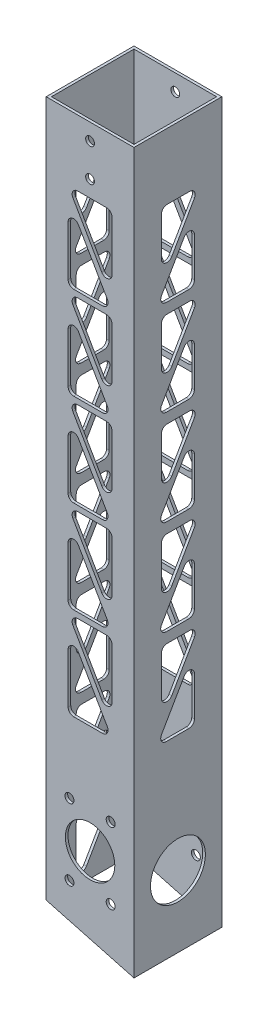
SolidWorks part; units mm, degrees
material "6061 Alloy"
ref_plane "Front Plane" through (0, 0, 0) normal (0, 0, 1) x (1, 0, 0)
ref_plane "Top Plane" through (0, 0, 0) normal (0, 1, 0) x (1, 0, 0)
ref_plane "Right Plane" through (0, 0, 0) normal (1, 0, 0) x (0, 0, -1)
sketch "Sketch1" plane through (0, 0, 0) normal (0, 1, 0) x (1, 0, 0)
  line L1 (25.4, 25.4) -> (-25.4, 25.4)
  line L2 (25.4, 25.4) -> (25.4, -25.4)
  line L3 (25.4, -25.4) -> (-25.4, -25.4)
  line L4 (-25.4, 25.4) -> (-25.4, -25.4)
  line L5 (25.4, 25.4) -> (-25.4, -25.4) construction
  line L6 (25.4, -25.4) -> (-25.4, 25.4) construction
  point P0 (0, 0)
  dimension "D1" = 50.8
extrude "Extrude-Thin1" add sketch "Sketch1" along normal blind 415.925 thin thin type one direction reverse wall 1.524
sketch "Sketch2" plane through (0, 0, 0) normal (0, 0, 1) x (1, 0, 0)
  line L0 (-36.2563, 68.2625) -> (38.5702, 68.2625) construction
  line L1 (-25.4, 0) -> (25.4, 0) construction
  line L2 (-25.4, 50.8) -> (25.4, 50.8) construction
  line L6 (25.4, 415.925) -> (25.4, 0) construction
  line L7 (-25.4, 415.925) -> (-25.4, 0) construction
  line L8 (-11.9062, 30.1778) -> (11.9063, 30.1778) construction
  line L9 (-11.9062, 71.4222) -> (11.9063, 71.4222) construction
  circle A0 centre (0, 50.8) radius 14.3002
  circle A1 centre (0, 50.8) radius 23.8125 construction
  circle A2 centre (-11.9062, 30.1778) radius 2.5908
  circle A3 centre (11.9063, 30.1778) radius 2.5908
  circle A4 centre (11.9063, 71.4222) radius 2.5908
  circle A5 centre (-11.9062, 71.4222) radius 2.5908
  point P11 (0, 50.8)
  dimension "D1" = 28.6004
  dimension "D3" = 17.4625
  dimension "D4" = 47.625
  dimension "D6" = 5.1816
  dimension "D2" = 50.8
  dimension "D5" = 60
extrude "Cut-Extrude1" cut sketch "Sketch2" along normal through all both and the other way through all
sketch "Sketch3" plane through (25.4, 0, 0) normal (1, 0, 0) x (0, 0, -1)
  line L0 (-25.4, 50.8) -> (25.4, 50.8) construction
  line L1 (-25.4, 65.1002) -> (-25.4, 36.4998) construction
  line L3 (25.4, 415.925) -> (25.4, 0) construction
  circle A0 centre (0, 41.275) radius 15.875
  point P9 (0, 50.8)
  dimension "D1" = 31.75
  dimension "D2" = 9.525
extrude "Cut-Extrude2" cut sketch "Sketch3" against normal up to surface (1.524 mm away) up to face at (23.876, 207.9625, 0)
sketch "Sketch4" plane through (0, 0, 25.4) normal (0, 0, 1) x (1, 0, 0)
  line L0 (-25.4, 415.925) -> (25.4, 415.925) construction
  circle A0 centre (0, 406.4) radius 2.54
  circle A1 centre (0, 387.35) radius 2.54
  dimension "D1" = 5.08
  dimension "D2" = 9.525
  dimension "D3" = 28.575
hole_wizard "#10 Clearance Hole1" positions "Sketch5" profile "Sketch6" hole size "#10" standard "ANSI Inch" end condition through all
sketch "Sketch5" plane through (0, 0, 25.4) normal (0, 0, 1) x (1, 0, 0)
  point P0 (0, 387.35)
  point P3 (0, 406.4)
sketch "Sketch6" plane through (0, 387.35, 25.4) normal (1, 0, 0) x (0, -1, 0)
  line L0 (0, 0) -> (0, 50.8)
  line L1 (0, 50.8) -> (2.5527, 50.8)
  line L2 (2.5527, 50.8) -> (2.5527, 0)
  line L5 (2.5527, 0) -> (0, 0)
  line L11 (0, -6.35) -> (0, 107.95) construction
  dimension "Thru Hole Dia." = 5.1054
  dimension "Thru Hole Depth" = 50.8
sketch "Sketch7" plane through (0, 0, 25.4) normal (0, 0, 1) x (1, 0, 0)
  line L0 (-12.7, 415.925) -> (-12.7, 0) construction
  line L1 (12.7, 415.925) -> (12.7, 0) construction
  line L2 (-12.7, 0) -> (-25.4, 0) construction
  line L3 (-25.4, 0) -> (25.4, 0) construction
  line L4 (-25.4, 415.925) -> (-25.4, 0) construction
  line L5 (12.7, 0) -> (25.4, 0) construction
  line L6 (-25.4, 415.925) -> (25.4, 415.925) construction
  line L7 (-12.7, 377.825) -> (12.7, 377.825) construction
  line L8 (-12.7, 79.375) -> (12.7, 79.375) construction
  line L9 (-7.2007, 377.825) -> (9.525, 377.825)
  line L10 (12.7, 374.65) -> (12.7, 345.6802)
  line L11 (6.7754, 344.0927) -> (-9.9504, 373.0625)
  line L12 (-9.525, 327.4809) -> (7.2007, 327.4809)
  line L13 (-12.7, 330.6559) -> (-12.7, 359.6257)
  line L14 (-6.7754, 361.2132) -> (9.9504, 332.2434)
  line L15 (15.0206, 323.4615) -> (17.7702, 325.049) construction
  line L16 (-7.2007, 324.3059) -> (9.525, 324.3059)
  line L17 (12.7, 321.1309) -> (12.7, 292.1611)
  line L18 (6.7754, 290.5736) -> (-9.9504, 319.5434)
  line L19 (-12.7, 277.1368) -> (-12.7, 306.1066)
  line L20 (-9.525, 273.9618) -> (7.2007, 273.9618)
  line L21 (-6.7754, 307.6941) -> (9.9504, 278.7243)
  line L34 (-7.2007, 377.825) -> (-7.2007, 324.3059) construction
  line L35 (-7.2007, 270.7868) -> (9.525, 270.7868)
  line L36 (12.7, 267.6118) -> (12.7, 238.642)
  line L37 (6.7754, 237.0545) -> (-9.9504, 266.0243)
  line L38 (-12.7, 223.6177) -> (-12.7, 252.5876)
  line L39 (-9.525, 220.4427) -> (7.2007, 220.4427)
  line L40 (-6.7754, 254.1751) -> (9.9504, 225.2052)
  line L41 (-7.2007, 217.2677) -> (9.525, 217.2677)
  line L42 (12.7, 214.0927) -> (12.7, 185.1229)
  line L43 (6.7754, 183.5354) -> (-9.9504, 212.5052)
  line L44 (-12.7, 170.0986) -> (-12.7, 199.0685)
  line L45 (-9.525, 166.9236) -> (7.2007, 166.9236)
  line L46 (-6.7754, 200.656) -> (9.9504, 171.6861)
  line L47 (-7.2007, 163.7486) -> (9.525, 163.7486)
  line L48 (12.7, 160.5736) -> (12.7, 131.6038)
  line L49 (6.7754, 130.0163) -> (-9.9504, 158.9861)
  line L50 (-12.7, 116.5795) -> (-12.7, 145.5494)
  line L51 (-9.525, 113.4045) -> (7.2007, 113.4045)
  line L52 (-6.7754, 147.1369) -> (9.9504, 118.167)
  arc A0 (-9.9504, 373.0625) -> (-7.2007, 377.825) centre (-7.2007, 374.65) cw
  arc A1 (9.525, 377.825) -> (12.7, 374.65) centre (9.525, 374.65) cw
  arc A2 (12.7, 345.6802) -> (6.7754, 344.0927) centre (9.525, 345.6802) cw
  arc A3 (9.9504, 332.2434) -> (7.2007, 327.4809) centre (7.2007, 330.6559) cw
  arc A4 (-12.7, 359.6257) -> (-6.7754, 361.2132) centre (-9.525, 359.6257) cw
  arc A5 (-12.7, 330.6559) -> (-9.525, 327.4809) centre (-9.525, 330.6559) ccw
  arc A6 (12.7, 292.1611) -> (6.7754, 290.5736) centre (9.525, 292.1611) cw
  arc A7 (-9.9504, 319.5434) -> (-7.2007, 324.3059) centre (-7.2007, 321.1309) cw
  arc A8 (9.525, 324.3059) -> (12.7, 321.1309) centre (9.525, 321.1309) cw
  arc A9 (-12.7, 306.1066) -> (-6.7754, 307.6941) centre (-9.525, 306.1066) cw
  arc A10 (-12.7, 277.1368) -> (-9.525, 273.9618) centre (-9.525, 277.1368) ccw
  arc A11 (9.9504, 278.7243) -> (7.2007, 273.9618) centre (7.2007, 277.1368) cw
  arc A12 (12.7, 238.642) -> (6.7754, 237.0545) centre (9.525, 238.642) cw
  arc A13 (-9.9504, 266.0243) -> (-7.2007, 270.7868) centre (-7.2007, 267.6118) cw
  arc A14 (9.525, 270.7868) -> (12.7, 267.6118) centre (9.525, 267.6118) cw
  arc A15 (-12.7, 252.5876) -> (-6.7754, 254.1751) centre (-9.525, 252.5876) cw
  arc A16 (-12.7, 223.6177) -> (-9.525, 220.4427) centre (-9.525, 223.6177) ccw
  arc A17 (9.9504, 225.2052) -> (7.2007, 220.4427) centre (7.2007, 223.6177) cw
  arc A18 (12.7, 185.1229) -> (6.7754, 183.5354) centre (9.525, 185.1229) cw
  arc A19 (-9.9504, 212.5052) -> (-7.2007, 217.2677) centre (-7.2007, 214.0927) cw
  arc A20 (9.525, 217.2677) -> (12.7, 214.0927) centre (9.525, 214.0927) cw
  arc A21 (-12.7, 199.0685) -> (-6.7754, 200.656) centre (-9.525, 199.0685) cw
  arc A22 (-12.7, 170.0986) -> (-9.525, 166.9236) centre (-9.525, 170.0986) ccw
  arc A23 (9.9504, 171.6861) -> (7.2007, 166.9236) centre (7.2007, 170.0986) cw
  arc A24 (12.7, 131.6038) -> (6.7754, 130.0163) centre (9.525, 131.6038) cw
  arc A25 (-9.9504, 158.9861) -> (-7.2007, 163.7486) centre (-7.2007, 160.5736) cw
  arc A26 (9.525, 163.7486) -> (12.7, 160.5736) centre (9.525, 160.5736) cw
  arc A27 (-12.7, 145.5494) -> (-6.7754, 147.1369) centre (-9.525, 145.5494) cw
  arc A28 (-12.7, 116.5795) -> (-9.525, 113.4045) centre (-9.525, 116.5795) ccw
  arc A29 (9.9504, 118.167) -> (7.2007, 113.4045) centre (7.2007, 116.5795) cw
  point P31 (12.7, 333.8309)
  point P34 (12.7, 327.4809)
  point P37 (-12.7, 371.475)
  point P40 (-12.7, 327.4809)
  dimension "D5" = 3.175
  dimension "D1" = 12.7
  dimension "D2" = 38.1
  dimension "D3" = 79.375
  dimension "D4" = 30
  dimension "D7" = 3.175
  dimension "D8" = 3.175
  dimension "D6" = 5
extrude "Cut-Extrude3" cut sketch "Sketch7" against normal through all
sketch "Sketch8" plane through (-25.4, 0, 0) normal (-1, 0, 0) x (0, 0, 1)
  line L0 (-12.2746, 377.825) -> (9.525, 377.825) construction
  line L1 (-6.7754, 377.825) -> (6.35, 377.825)
  line L2 (9.525, 374.65) -> (9.525, 351.9162)
  line L3 (3.6004, 350.3287) -> (-9.525, 373.0625)
  line L4 (-6.35, 328.9544) -> (6.7754, 328.9544)
  line L5 (-9.525, 332.1294) -> (-9.525, 354.8632)
  line L6 (-3.6004, 356.4507) -> (9.525, 333.7169)
  line L7 (0.8507, 348.7412) -> (3.6004, 350.3287) construction
  line L8 (-9.525, 415.925) -> (-9.525, 0) construction
  line L9 (-25.4, 0) -> (25.4, 0) construction
  line L10 (9.525, 0) -> (9.525, 415.925) construction
  line L11 (-25.4, 415.925) -> (25.4, 415.925) construction
  line L12 (-9.525, 377.825) -> (-25.4, 377.825) construction
  line L13 (-25.4, 415.925) -> (-25.4, 0) construction
  line L14 (9.525, 377.825) -> (25.4, 377.825) construction
  line L15 (25.4, 415.925) -> (25.4, 0) construction
  line L16 (-6.35, 273.9879) -> (6.7754, 273.9879)
  line L17 (-9.525, 277.1629) -> (-9.525, 299.8967)
  line L18 (-3.6004, 301.4842) -> (9.525, 278.7504)
  line L19 (9.525, 319.6834) -> (9.525, 296.9496)
  line L20 (3.6004, 295.3621) -> (-9.525, 318.0959)
  line L21 (-6.7754, 322.8584) -> (6.35, 322.8584)
  line L22 (-6.35, 219.0213) -> (6.7754, 219.0213)
  line L23 (-9.525, 222.1963) -> (-9.525, 244.9301)
  line L24 (-3.6004, 246.5176) -> (9.525, 223.7838)
  line L25 (9.525, 264.7169) -> (9.525, 241.9831)
  line L26 (3.6004, 240.3956) -> (-9.525, 263.1294)
  line L27 (-6.7754, 267.8919) -> (6.35, 267.8919)
  line L28 (-6.35, 164.0547) -> (6.7754, 164.0547)
  line L29 (-9.525, 167.2297) -> (-9.525, 189.9635)
  line L30 (-3.6004, 191.551) -> (9.525, 168.8172)
  line L31 (9.525, 209.7503) -> (9.525, 187.0165)
  line L32 (3.6004, 185.429) -> (-9.525, 208.1628)
  line L33 (-6.7754, 212.9253) -> (6.35, 212.9253)
  line L34 (-25.4, 87.3125) -> (25.4, 87.3125) construction
  line L35 (-6.35, 109.0882) -> (6.7754, 109.0882)
  line L36 (-9.525, 112.2632) -> (-9.525, 134.997)
  line L37 (-3.6004, 136.5845) -> (9.525, 113.8507)
  line L38 (9.525, 154.7837) -> (9.525, 132.0499)
  line L39 (3.6004, 130.4624) -> (-9.525, 153.1962)
  line L40 (-6.7754, 157.9587) -> (6.35, 157.9587)
  line L41 (-6.35, 54.1216) -> (6.7754, 54.1216)
  line L42 (-9.525, 57.2966) -> (-9.525, 80.0304)
  line L43 (-3.6004, 81.6179) -> (9.525, 58.8841)
  line L44 (9.525, 99.8172) -> (9.525, 77.0834)
  line L45 (3.6004, 75.4959) -> (-9.525, 98.2297)
  line L46 (-6.7754, 102.9922) -> (6.35, 102.9922)
  line L50 (9.525, 44.8506) -> (9.525, 22.1168)
  line L51 (3.6004, 20.5293) -> (-9.525, 43.2631)
  line L52 (-6.7754, 48.0256) -> (6.35, 48.0256)
  line L53 (-6.35, -0.8449) -> (6.7754, -0.8449) [skipped]
  line L54 (-3.6004, 26.6514) -> (9.525, 3.9176) [skipped]
  line L55 (-9.525, 2.3301) -> (-9.525, 25.0639) [skipped]
  arc A0 (-9.525, 373.0625) -> (-6.7754, 377.825) centre (-6.7754, 374.65) cw
  arc A1 (6.35, 377.825) -> (9.525, 374.65) centre (6.35, 374.65) cw
  arc A2 (9.525, 351.9162) -> (3.6004, 350.3287) centre (6.35, 351.9162) cw
  arc A3 (9.525, 333.7169) -> (6.7754, 328.9544) centre (6.7754, 332.1294) cw
  arc A4 (-9.525, 354.8632) -> (-3.6004, 356.4507) centre (-6.35, 354.8632) cw
  arc A5 (-9.525, 332.1294) -> (-6.35, 328.9544) centre (-6.35, 332.1294) ccw
  arc A6 (-9.525, 277.1629) -> (-6.35, 273.9879) centre (-6.35, 277.1629) ccw
  arc A7 (-9.525, 299.8967) -> (-3.6004, 301.4842) centre (-6.35, 299.8967) cw
  arc A8 (9.525, 278.7504) -> (6.7754, 273.9879) centre (6.7754, 277.1629) cw
  arc A9 (9.525, 296.9496) -> (3.6004, 295.3621) centre (6.35, 296.9496) cw
  arc A10 (6.35, 322.8584) -> (9.525, 319.6834) centre (6.35, 319.6834) cw
  arc A11 (-9.525, 318.0959) -> (-6.7754, 322.8584) centre (-6.7754, 319.6834) cw
  arc A12 (-9.525, 222.1963) -> (-6.35, 219.0213) centre (-6.35, 222.1963) ccw
  arc A13 (-9.525, 244.9301) -> (-3.6004, 246.5176) centre (-6.35, 244.9301) cw
  arc A14 (9.525, 223.7838) -> (6.7754, 219.0213) centre (6.7754, 222.1963) cw
  arc A15 (9.525, 241.9831) -> (3.6004, 240.3956) centre (6.35, 241.9831) cw
  arc A16 (6.35, 267.8919) -> (9.525, 264.7169) centre (6.35, 264.7169) cw
  arc A17 (-9.525, 263.1294) -> (-6.7754, 267.8919) centre (-6.7754, 264.7169) cw
  arc A18 (-9.525, 167.2297) -> (-6.35, 164.0547) centre (-6.35, 167.2297) ccw
  arc A19 (-9.525, 189.9635) -> (-3.6004, 191.551) centre (-6.35, 189.9635) cw
  arc A20 (9.525, 168.8172) -> (6.7754, 164.0547) centre (6.7754, 167.2297) cw
  arc A21 (9.525, 187.0165) -> (3.6004, 185.429) centre (6.35, 187.0165) cw
  arc A22 (6.35, 212.9253) -> (9.525, 209.7503) centre (6.35, 209.7503) cw
  arc A23 (-9.525, 208.1628) -> (-6.7754, 212.9253) centre (-6.7754, 209.7503) cw
  arc A24 (-9.525, 112.2632) -> (-6.35, 109.0882) centre (-6.35, 112.2632) ccw
  arc A25 (-9.525, 134.997) -> (-3.6004, 136.5845) centre (-6.35, 134.997) cw
  arc A26 (9.525, 113.8507) -> (6.7754, 109.0882) centre (6.7754, 112.2632) cw
  arc A27 (9.525, 132.0499) -> (3.6004, 130.4624) centre (6.35, 132.0499) cw
  arc A28 (6.35, 157.9587) -> (9.525, 154.7837) centre (6.35, 154.7837) cw
  arc A29 (-9.525, 153.1962) -> (-6.7754, 157.9587) centre (-6.7754, 154.7837) cw
  arc A30 (-9.525, 57.2966) -> (-6.35, 54.1216) centre (-6.35, 57.2966) ccw
  arc A31 (-9.525, 80.0304) -> (-3.6004, 81.6179) centre (-6.35, 80.0304) cw
  arc A32 (9.525, 58.8841) -> (6.7754, 54.1216) centre (6.7754, 57.2966) cw
  arc A33 (9.525, 77.0834) -> (3.6004, 75.4959) centre (6.35, 77.0834) cw
  arc A34 (6.35, 102.9922) -> (9.525, 99.8172) centre (6.35, 99.8172) cw
  arc A35 (-9.525, 98.2297) -> (-6.7754, 102.9922) centre (-6.7754, 99.8172) cw
  arc A39 (9.525, 22.1168) -> (3.6004, 20.5293) centre (6.35, 22.1168) cw
  arc A40 (6.35, 48.0256) -> (9.525, 44.8506) centre (6.35, 44.8506) cw
  arc A41 (-9.525, 43.2631) -> (-6.7754, 48.0256) centre (-6.7754, 44.8506) cw
  arc A42 (9.525, 3.9176) -> (6.7754, -0.8449) centre (6.7754, 2.3301) cw [skipped]
  arc A43 (-9.525, 25.0639) -> (-3.6004, 26.6514) centre (-6.35, 25.0639) cw [skipped]
  arc A44 (-9.525, 2.3301) -> (-6.35, -0.8449) centre (-6.35, 2.3301) ccw [skipped]
  point P7 (9.525, 381.5918)
  point P131 (3.962, 352.9988)
  point P150 (7.1718, 19.05)
  dimension "D2" = 3.175
  dimension "D1" = 30
  dimension "D3" = 38.1
  dimension "D4" = 15.875
  dimension "D5" = 3.175
  dimension "D7" = 19.05
  dimension "D8" = 87.3125
  dimension "D6" = 7
extrude "Cut-Extrude4" cut sketch "Sketch8" against normal through all contours A14 L24 A13 L23 A12 L22 | A17 L26 A15 L25 A16 L27 | A8 L18 A7 L17 A6 L16 | A11 L20 A9 L19 A10 L21 | L5 A5 L4 A3 L6 A4 | A2 L2 A1 L1 A0 L3 | A23 L32 A21 L31 A22 L33 | A20 L30 A19 L29 A18 L28 | A29 L39 A27 L38 A28 L40 | A26 L37 A25 L36 A24 L35 region at (-25.4, 366.19, 2.0868) region at (-25.4, 340.5895, -2.0868) region at (-25.4, 285.6229, -2.0868) region at (-25.4, 311.2234, 2.0868) region at (-25.4, 230.6563, -2.0868) region at (-25.4, 256.2569, 2.0868) region at (-25.4, 175.6898, -2.0868) region at (-25.4, 201.2903, 2.0868) region at (-25.4, 120.7232, -2.0868) region at (-25.4, 146.3237, 2.0868)
extrude "Cut-Extrude5" cut sketch "Sketch8<4>" against normal up to next contours A41 L51 A39 L50 A40 L52 | A32 L43 A31 L42 A30 L41 | A35 L45 A33 L44 A34 L46 region at (-25.4, 65.7566, -2.0868) region at (-25.4, 91.3572, 2.0868) region at (-25.4, 36.3906, 2.0868)
sketch "Sketch8<4>" plane through (-25.4, 0, 0) normal (-1, 0, 0) x (0, 0, 1) same geometry as "Sketch8"
sketch "Sketch9" plane through (0, 0, 25.4) normal (0, 0, 1) x (1, 0, 0)
  line L0 (25.4, 0) -> (-25.4, 13.6118)
  line L1 (-25.4, 415.925) -> (-25.4, 0) construction
  line L2 (-25.4, 13.6118) -> (-25.4, 0)
  line L3 (-25.4, 0) -> (25.4, 0)
  dimension "D1" = 15
extrude "Cut-Extrude6" cut sketch "Sketch9" against normal through all
